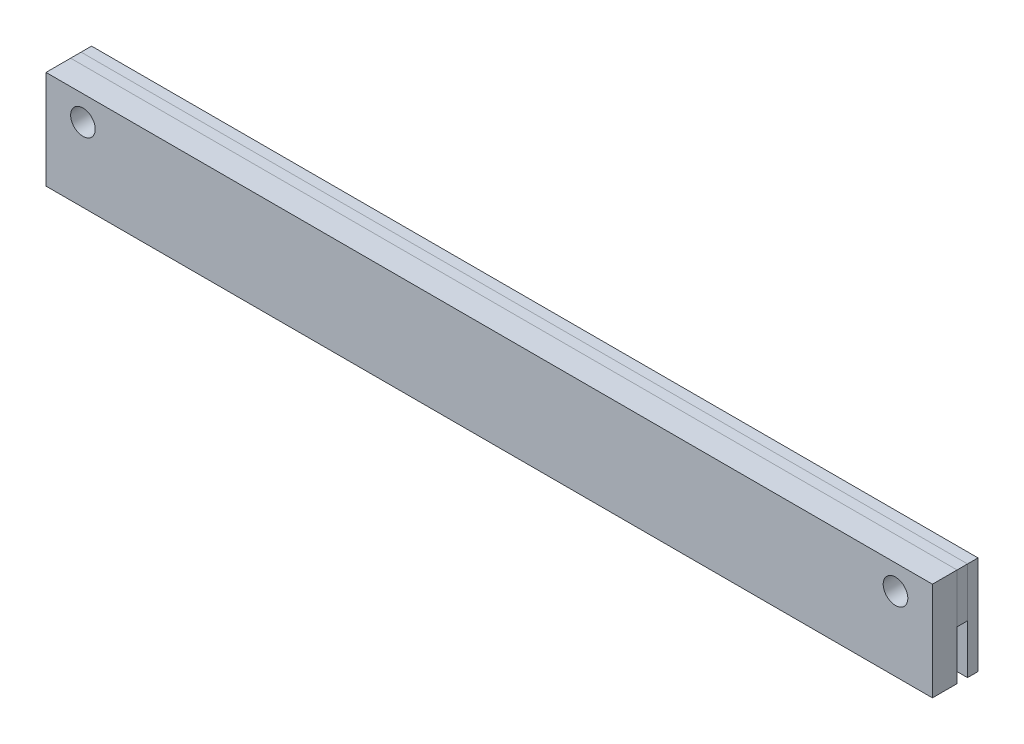
SolidWorks part; units mm, degrees
ref_plane "Front" through (0, 0, 0) normal (0, 0, 1) x (1, 0, 0)
ref_plane "Top" through (0, 0, 0) normal (0, 1, 0) x (1, 0, 0)
ref_plane "Right" through (0, 0, 0) normal (1, 0, 0) x (0, 0, -1)
sketch "Sketch2" plane through (0, 0, 0) normal (1, 0, 0) x (0, 0, -1)
  line L1 (-7.7, 6.35) -> (-1.35, 6.35)
  line L2 (-7.7, 6.35) -> (-7.7, -19.05)
  line L3 (-7.7, -19.05) -> (-1.35, -19.05)
  line L4 (-1.35, 6.35) -> (-1.35, -19.05)
  line L5 (-7.7, 6.35) -> (-1.35, -19.05) construction
  line L6 (-7.7, -19.05) -> (-1.35, 6.35) construction
  line L7 (-1.35, 6.35) -> (1.35, 6.35)
  line L8 (-1.35, 6.35) -> (-1.35, -6.35)
  line L9 (-1.35, -6.35) -> (1.35, -6.35)
  line L10 (1.35, 6.35) -> (1.35, -6.35)
  line L11 (-1.35, 6.35) -> (1.35, -6.35) construction
  line L12 (-1.35, -6.35) -> (1.35, 6.35) construction
  line L13 (1.35, 6.35) -> (4.05, 6.35)
  line L14 (1.35, 6.35) -> (1.35, -19.05)
  line L15 (1.35, -19.05) -> (4.05, -19.05)
  line L16 (4.05, 6.35) -> (4.05, -19.05)
  line L17 (1.35, 6.35) -> (4.05, -19.05) construction
  line L18 (1.35, -19.05) -> (4.05, 6.35) construction
  point P4 (-4.525, -6.35)
  point P8 (0, 0)
  point P12 (2.7, -6.35)
  dimension "D1" = 12.7
  dimension "D2" = 12.7
  dimension "D3" = 2.7
  dimension "D4" = 6.35
  dimension "D5" = 2.7
extrude "Boss-Extrude1" add sketch "Sketch2" along normal mid plane 228.6 contours L4 L1 L2 L3 region at (0, -6.35, 4.525)
extrude "Boss-Extrude2" add sketch "Sketch2<4>" along normal mid plane 228.6 separate body contours L10 L7 L4 L9 region at (0, 0, 0)
sketch "Sketch2<4>" plane through (0, 0, 0) normal (1, 0, 0) x (0, 0, -1) same geometry as "Sketch2"
extrude "Boss-Extrude3" add sketch "Sketch2<5>" along normal mid plane 228.6 separate body contours L16 L13 L10 L14 L15 region at (0, -6.35, -2.7)
sketch "Sketch2<5>" plane through (0, 0, 0) normal (1, 0, 0) x (0, 0, -1) same geometry as "Sketch2"
sketch "Sketch4" plane through (0, 0, 7.7) normal (0, 0, 1) x (1, 0, 0)
  line L0 (-104.775, 0) -> (-114.3, 0) construction
  line L1 (-114.3, 6.35) -> (-114.3, -19.05) construction
  line L2 (-104.775, 0) -> (-104.775, 6.35) construction
  line L3 (114.3, 6.35) -> (-114.3, 6.35) construction
  line L4 (104.775, 0) -> (114.3, 0) construction
  line L5 (114.3, 6.35) -> (114.3, -19.05) construction
  line L6 (104.775, 0) -> (104.775, 6.35) construction
  circle A0 centre (-104.775, 0) radius 3.175
  circle A1 centre (104.775, 0) radius 3.175
  dimension "D1" = 6.35
  dimension "D2" = 6.35
extrude "Cut-Extrude4" cut sketch "Sketch4" against normal up to surface (11.75 mm away) contours A0 | A1 region at (-104.775, 0, 7.7) region at (104.775, 0, 7.7) up to face at (0, -6.35, -4.05)
